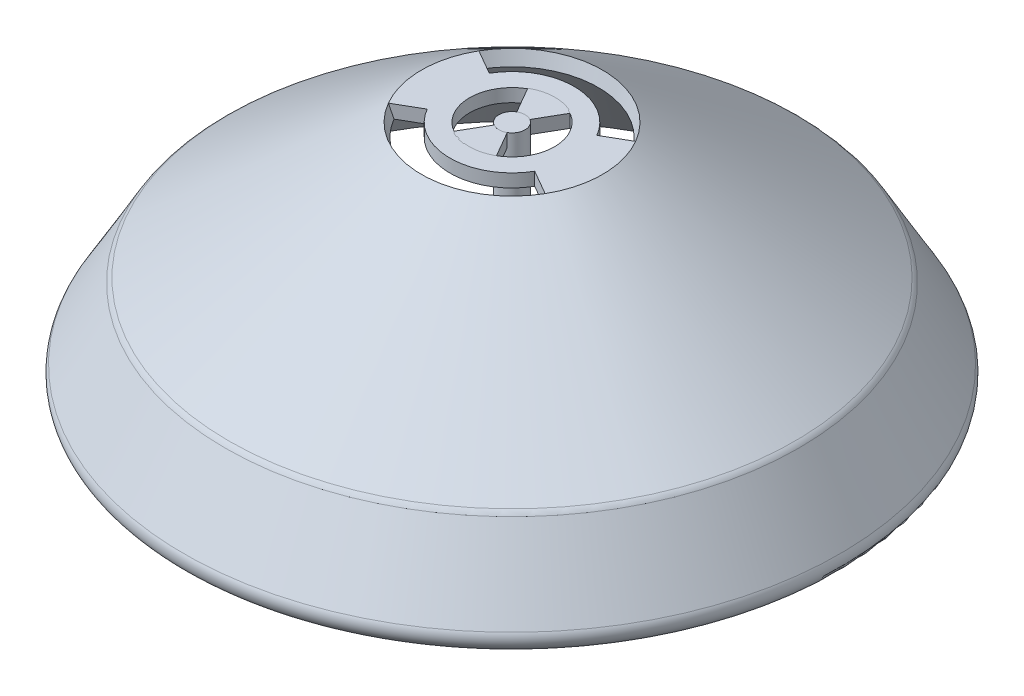
SolidWorks part; units mm, degrees
ref_plane "Front Plane" through (0, 0, 0) normal (0, 0, 1) x (1, 0, 0)
ref_plane "Top Plane" through (0, 0, 0) normal (0, 1, 0) x (1, 0, 0)
ref_plane "Right Plane" through (0, 0, 0) normal (1, 0, 0) x (0, 0, -1)
sketch "Sketch1" plane through (0, 0, 0) normal (0, 0, 1) x (1, 0, 0)
  line L1 (9.525, 104.902) -> (9.525, 95.25)
  line L2 (3.683, 97.79) -> (3.683, 95.25)
  line L4 (3.683, 95.25) -> (9.525, 95.25)
  line L5 (3.683, 97.79) -> (6.35, 97.79)
  line L6 (-9.525, 104.902) -> (-9.525, 95.25)
  line L9 (-3.683, 95.25) -> (-9.525, 95.25)
  line L13 (-3.683, 97.79) -> (-3.683, 95.25)
  line L16 (-3.683, 97.79) -> (-6.35, 97.79)
  line L17 (-9.525, 104.902) -> (9.525, 104.902)
  line L18 (-6.35, 97.79) -> (-6.35, 101.6)
  line L19 (0, 133.35) -> (0, 94.2799)
  line L20 (6.35, 101.6) -> (9.525, 101.6)
  line L21 (-6.35, 101.6) -> (6.35, 101.6)
  line L22 (6.35, 101.6) -> (6.35, 97.79)
  line L24 (8.255, 133.35) -> (8.255, 130.81)
  line L25 (12.065, 133.35) -> (12.065, 130.81)
  line L28 (9.525, 101.6) -> (-6.35, 101.6)
  line L31 (-6.35, 101.6) -> (-9.525, 101.6)
  line L32 (0, 130.81) -> (16.7852, 130.81)
  line L33 (16.7852, 130.81) -> (53.5102, 105.0949)
  line L34 (53.5102, 105.0949) -> (62.7536, 89.0848)
  line L35 (-2.54, 133.35) -> (-2.54, 104.902)
  line L36 (62.2037, 88.7673) -> (64.9533, 90.3548) construction
  line L37 (2.54, 133.35) -> (2.54, 104.902)
  line L38 (-62.7536, 89.0848) -> (-64.9533, 90.3548)
  line L39 (-55.4283, 106.8526) -> (-64.9533, 90.3548)
  line L40 (-53.5102, 105.0949) -> (-62.7536, 89.0848)
  line L41 (-8.255, 133.35) -> (-8.255, 130.81)
  line L42 (-12.065, 133.35) -> (-12.065, 130.81)
  line L43 (-16.7852, 130.81) -> (-53.5102, 105.0949)
  line L44 (-17.5861, 133.35) -> (-55.4283, 106.8526)
  line L45 (0, 133.35) -> (-17.5861, 133.35)
  line L46 (0, 130.81) -> (-16.7852, 130.81)
  line L47 (-17.5861, 133.35) -> (-16.7852, 130.81)
  line L48 (2.54, 133.35) -> (2.54, 94.2799) construction
  line L49 (-2.54, 133.35) -> (-2.54, 94.2799) construction
  line L50 (17.5861, 133.35) -> (16.7852, 130.81)
  line L73 (0, 133.35) -> (17.5861, 133.35)
  line L74 (17.5861, 133.35) -> (55.4283, 106.8526)
  line L78 (55.4283, 106.8526) -> (64.9533, 90.3548)
  line L82 (62.7536, 89.0848) -> (64.9533, 90.3548)
  line L86 (10.16, 133.35) -> (10.16, 130.81) construction
  line L90 (-55.4283, 106.8526) -> (-64.9533, 90.3548)
  line L92 (-17.5861, 133.35) -> (-55.4283, 106.8526)
  line L104 (0, 133.35) -> (-17.5861, 133.35)
  line L105 (60.9337, 90.967) -> (61.4836, 91.2845) construction
  line L106 (53.5102, 105.0949) -> (61.4836, 91.2845) construction
  point P11 (3.81, 25.4)
  point P14 (10.7436, 6.35)
  point P18 (-0.6484, 19.0832)
  point P19 (6.2973, 0)
  point P24 (12.7, 0)
  point P26 (12.7, 25.4)
  point P28 (0, 38.1)
  point P31 (12.1451, 41.8131)
  point P32 (0, 38.1)
  point P33 (19.05, 38.1)
  point P57 (0, 101.6)
  point P72 (-1.27, 101.6)
  point P73 (-1.27, -11.7576)
  point P74 (1.27, 101.6)
  point P75 (1.27, -11.7576)
  point P84 (0, 104.902)
  point P94 (-3.81, 104.902)
  dimension "D1" = 2.54
  dimension "D2" = 2.54
  dimension "D3" = 2.54
  dimension "D4" = 1.905
  dimension "D5" = 1.905
revolve "Revolve4" add sketch "Sketch1" angle 360 about L19 region at (4.7625, 103.251, 0)
revolve "Revolve5" add sketch "Sketch1<21>" angle 90 mid plane about L19 region at (7.2029, 97.9459, 0) region at (-7.2029, 97.9459, 0)
sketch "Sketch1<21>" plane through (0, 0, 0) normal (0, 0, 1) x (1, 0, 0) same geometry as "Sketch1"
revolve "Revolve7" add sketch "Sketch1<24>" angle 360 about L19 region at (1.27, 117.856, 0) region at (1.27, 132.08, 0) region at (10.16, 132.08, 0) region at (42.6441, 112.8479, 0)
sketch "Sketch1<24>" plane through (0, 0, 0) normal (0, 0, 1) x (1, 0, 0) same geometry as "Sketch1"
revolve "Revolve9" add sketch "Sketch1<29>" angle 60 mid plane about L19 region at (14.6306, 132.1131, 0) region at (-14.6306, 132.1131, 0)
sketch "Sketch1<29>" plane through (0, 0, 0) normal (0, 0, 1) x (1, 0, 0) same geometry as "Sketch1"
sketch "Sketch2" plane through (0, 0, 0) normal (1, 0, 0) x (0, 0, -1)
  line L0 (0, 133.35) -> (0, 130.81)
  line L1 (8.7931, 133.35) -> (-8.7931, 133.35) construction
  line L2 (-23.1679, 130.81) -> (23.1679, 130.81)
  line L3 (0, 133.35) -> (0, 130.8026)
  line L5 (-2.54, 133.35) -> (2.54, 133.35)
  line L6 (2.54, 133.35) -> (10.922, 133.35) construction
  line L7 (-8.382, 133.35) -> (8.382, 133.35)
  line L8 (8.382, 133.35) -> (8.382, 130.81)
  line L10 (2.54, 130.81) -> (2.54, 133.35)
  line L11 (-8.382, 133.35) -> (-8.382, 130.81)
  line L12 (-2.54, 130.81) -> (-2.54, 133.35)
revolve "Revolve10" add sketch "Sketch2" angle 60 mid plane about L0 region at (0, 132.08, 5.461) region at (0, 132.08, -5.461)
fillet "Fillet1" radius 2.54 1 edges at (0, 90.3548, 64.9533)
fillet "Fillet2" radius 2.54 1 edges at (0, 106.8526, 55.4283)
